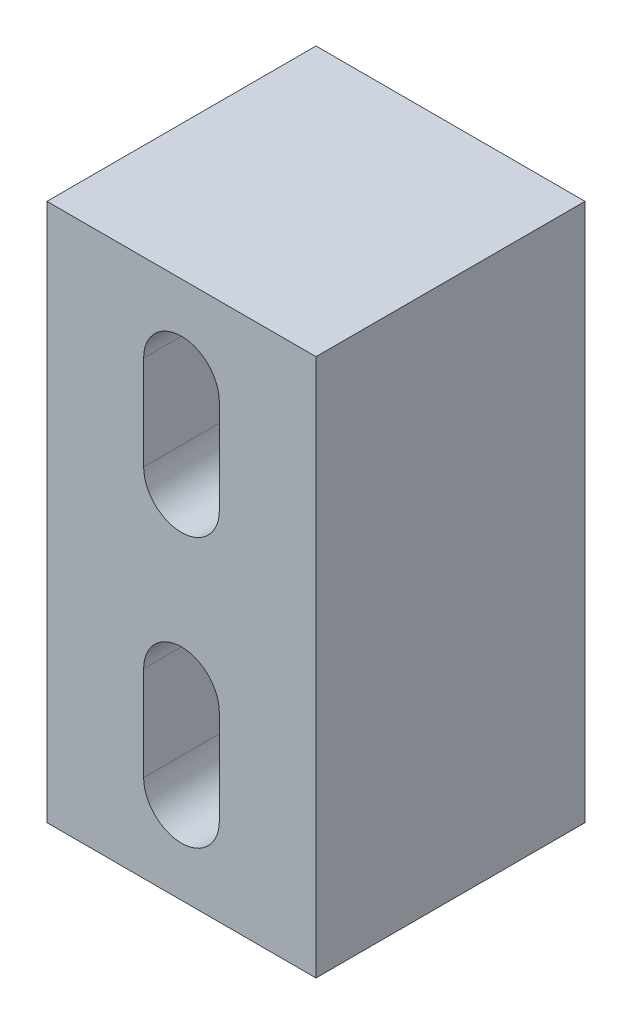
SolidWorks part; units mm, degrees
material "Pure Lead"
ref_plane "Front Plane" through (0, 0, 0) normal (0, 0, 1) x (1, 0, 0)
ref_plane "Top Plane" through (0, 0, 0) normal (0, 1, 0) x (1, 0, 0)
ref_plane "Right Plane" through (0, 0, 0) normal (1, 0, 0) x (0, 0, -1)
sketch "Sketch1" plane through (0, 0, 0) normal (0, 0, 1) x (1, 0, 0)
  line L1 (-12.7, 25.4) -> (12.7, 25.4)
  line L2 (-12.7, 25.4) -> (-12.7, -25.4)
  line L3 (-12.7, -25.4) -> (12.7, -25.4)
  line L4 (12.7, 25.4) -> (12.7, -25.4)
  line L5 (-12.7, 25.4) -> (12.7, -25.4) construction
  line L6 (-12.7, -25.4) -> (12.7, 25.4) construction
  point P0 (0, 0)
  dimension "D1" = 25.4
  dimension "D2" = 50.8
extrude "Boss-Extrude1" add sketch "Sketch1" along normal blind 25.4
hole_wizard "CBORE SLOT for #6 Socket Head Cap Screw1" positions "Sketch2" profile "Sketch3" size "#6" standard "ANSI Inch" slot yes end condition up to next
sketch "Sketch2" plane through (0, 0, 25.4) normal (0, 0, 1) x (1, 0, 0)
  line L0 (0, 6.35) -> (0, 19.05) construction
  line L1 (0, 12.7) -> (0, 0) construction
  line L2 (0, 12.7) -> (0, -12.7) construction
  point P0 (0, 12.7)
  point P11 (0, -12.7)
  dimension "D1" = 12.7
  dimension "D2" = 25.4
  dimension "D3" = 12.7
sketch "Sketch3" plane through (0, 12.7, 25.4) normal (1, 0, 0) x (0, -1, 0)
  line L0 (0, 0) -> (0, 25.4)
  line L1 (0, 25.4) -> (1.8986, 25.4)
  line L3 (1.8986, 25.4) -> (1.8986, 8.5052)
  line L4 (1.8986, 8.5052) -> (3.5725, 8.5052)
  line L5 (3.5725, 8.5052) -> (3.5725, 0)
  line L7 (3.5725, 0) -> (0, 0)
  line L11 (0, -6.35) -> (0, 107.95) construction
  dimension "Thru Hole Dia." = 3.7973
  dimension "Thru Hole Depth" = 25.4
  dimension "C'Bore Dia." = 7.145
  dimension "C'Bore Depth" = 8.5052
equation "\"D3@Sketch2\"=\"D2@Sketch2\"/2"
